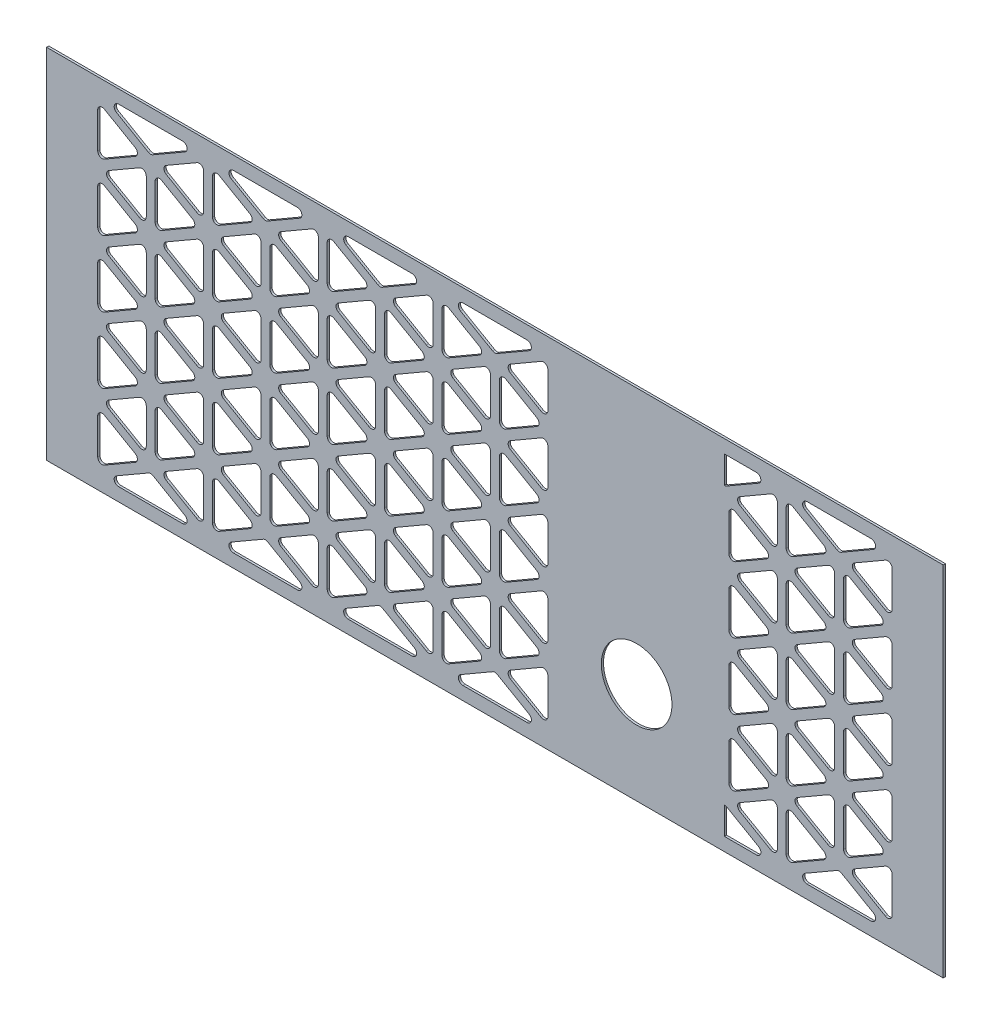
SolidWorks part; units mm, degrees
note: The reader was unsure of these and kept them because the rebuilt part matched: shared geometry of "Sketch3<5>".
ref_plane "Front Plane" through (0, 0, 0) normal (0, 0, 1) x (1, 0, 0)
ref_plane "Top Plane" through (0, 0, 0) normal (0, 1, 0) x (1, 0, 0)
ref_plane "Right Plane" through (0, 0, 0) normal (1, 0, 0) x (0, 0, -1)
sketch "Sketch1" plane through (0, 0, 0) normal (0, 0, 1) x (1, 0, 0)
  line L1 (-101.5, 40.5) -> (101.5, 40.5)
  line L2 (-101.5, 40.5) -> (-101.5, -40.5)
  line L3 (-101.5, -40.5) -> (101.5, -40.5)
  line L4 (101.5, 40.5) -> (101.5, -40.5)
  line L5 (-101.5, 40.5) -> (101.5, -40.5) construction
  line L6 (-101.5, -40.5) -> (101.5, 40.5) construction
  point P0 (0, 0)
  dimension "D1" = 81
  dimension "D2" = 203
extrude "Boss-Extrude1" add sketch "Sketch1" along normal mid plane 0.5
sketch "Sketch3" plane through (0, 0, 0.25) normal (0, 0, 1) x (1, 0, 0)
  line L0 (-90.93, -22.5) -> (-90.93, -37.5) construction
  line L1 (-90.93, -37.5) -> (-77.9396, -30) construction
  line L2 (-77.9396, -30) -> (-90.93, -22.5) construction
  line L3 (-77.9396, -30) -> (-77.9396, -15) construction
  line L4 (-77.9396, -15) -> (-90.93, -22.5) construction
  line L7 (-89.93, -24.2321) -> (-89.93, -35.7679) construction
  line L8 (-89.93, -35.7679) -> (-79.9396, -30) construction
  line L9 (-79.9396, -30) -> (-89.93, -24.2321) construction
  line L10 (-78.9396, -16.7321) -> (-78.9396, -28.2679) construction
  line L11 (-78.9396, -28.2679) -> (-88.93, -22.5) construction
  line L12 (-88.93, -22.5) -> (-78.9396, -16.7321) construction
  line L13 (-101.5, -40.5) -> (101.5, -40.5) construction
  line L15 (-101.5, 40.5) -> (-101.5, -40.5) construction
  line L16 (-90.93, -30) -> (-89.93, -30) construction
  line L17 (-84.4348, -26.25) -> (-84.9348, -27.116) construction
  line L18 (-84.4348, -33.75) -> (-84.9348, -32.884) construction
  line L19 (-89.93, -25.9641) -> (-89.93, -34.0359)
  line L20 (-88.43, -34.9019) -> (-81.4396, -30.866)
  line L21 (-81.4396, -29.134) -> (-88.43, -25.0981)
  line L23 (-78.9396, -18.4641) -> (-78.9396, -26.5359)
  line L24 (-87.43, -23.366) -> (-80.4396, -27.4019)
  line L25 (-87.43, -21.634) -> (-80.4396, -17.5981)
  arc A0 (-88.43, -34.9019) -> (-89.93, -34.0359) centre (-88.93, -34.0359) cw
  arc A1 (-81.4396, -29.134) -> (-81.4396, -30.866) centre (-81.9396, -30) cw
  arc A2 (-89.93, -25.9641) -> (-88.43, -25.0981) centre (-88.93, -25.9641) cw
  arc A4 (-87.43, -23.366) -> (-87.43, -21.634) centre (-86.93, -22.5) cw
  arc A5 (-78.9396, -26.5359) -> (-80.4396, -27.4019) centre (-79.9396, -26.5359) cw
  arc A6 (-78.9396, -18.4641) -> (-80.4396, -17.5981) centre (-79.9396, -18.4641) ccw
  dimension "D7" = 1
  dimension "D9" = 1
  dimension "D1" = 2
  dimension "D2" = 15
  dimension "D3" = 3
  dimension "D4" = 10.57
  dimension "D5" = 1
  dimension "D6" = 1
  dimension "length" = 12.9904
extrude "Cut-Extrude3" cut sketch "Sketch3" against normal through all contours L21 A2 L19 A0 L20 A1
extrude "Cut-Extrude4" cut sketch "Sketch3<5>" against normal through all contours A6 L23 A5 L24 A4 L25
sketch "Sketch3<5>" plane through (0, 0, 0.25) normal (0, 0, 1) x (1, 0, 0) same geometry as "Sketch3"
pattern_linear "LPattern2" count 5 spacing 15 along (0, 1, 0) of "Cut-Extrude3"
pattern_linear "LPattern3" count 4 spacing 15 along (0, 1, 0) of "Cut-Extrude4"
ref_plane "Plane1" through (-77.9396, 0, 0) normal (-1, 0, 0) x (0, 0, 1)
mirror "Mirror1" about plane through (-77.9396, 0, 0) normal (-1, 0, 0) of "LPattern2", "LPattern3", "Cut-Extrude3", "Cut-Extrude4"
pattern_linear "LPattern4" count 7 spacing 25.98 along (1, 0, 0) of "LPattern3", "LPattern2", "Mirror1", "Cut-Extrude3", "Cut-Extrude4"
sketch "Sketch7" plane through (0, 0, 0.25) normal (0, 0, 1) x (1, 0, 0)
  line L0 (-90.93, -37.5) -> (-77.94, -30) construction
  line L1 (-77.94, -30) -> (-64.95, -37.5) construction
  line L2 (-64.95, -37.5) -> (-90.93, -37.5) construction
  line L3 (-101.5, -40.5) -> (101.5, -40.5) construction
  line L4 (-101.5, 40.5) -> (-101.5, -40.5) construction
  line L5 (-78.44, -31.4434) -> (-85.6981, -35.634)
  line L6 (-85.1981, -37.5) -> (-70.6819, -37.5)
  line L7 (-70.1819, -35.634) -> (-77.44, -31.4434)
  arc A0 (-85.1981, -37.5) -> (-85.6981, -35.634) centre (-85.1981, -36.5) cw
  arc A1 (-70.1819, -35.634) -> (-70.6819, -37.5) centre (-70.6819, -36.5) cw
  arc A2 (-77.44, -31.4434) -> (-78.44, -31.4434) centre (-77.94, -32.3094) ccw
  point P9 (-71.445, -33.75)
  dimension "D7" = 1
  dimension "D1" = 10.57
  dimension "D2" = 3
  dimension "D3" = 25.98
  dimension "D4" = 7.5
  dimension "D5" = 1
  dimension "D6" = 1
extrude "Cut-Extrude5" cut sketch "Sketch7" against normal through all
pattern_linear "LPattern5" count 7 spacing 25.98 along (1, 0, 0) of "Cut-Extrude5"
ref_plane "Plane2" [suppressed] through (0, 0, 0) normal (0, -1, 0) x (-1, 0, 0)
mirror "Mirror2" about plane through (0, 0, 0) normal (0, -1, 0) of "LPattern5", "Cut-Extrude5"
sketch "Sketch8" plane through (0, 0, 0.25) normal (0, 0, 1) x (1, 0, 0)
  line L1 (13.99, 40.5) -> (51.96, 40.5)
  line L2 (13.99, 40.5) -> (13.99, -40.5)
  line L3 (13.99, -40.5) -> (51.96, -40.5)
  line L4 (101.5, -40.5) -> (101.5, 40.5)
  line L5 (101.5, 40.5) -> (-101.5, 40.5)
  line L6 (-101.5, 40.5) -> (-101.5, -40.5)
  line L7 (-101.5, -40.5) -> (101.5, -40.5)
  line L8 (101.5, -40.5) -> (101.5, 40.5)
  line L9 (101.5, 40.5) -> (-101.5, 40.5)
  line L10 (-101.5, 40.5) -> (-101.5, -40.5)
  line L11 (-101.5, -40.5) -> (101.5, -40.5)
  line L12 (51.96, 40.5) -> (51.96, -40.5)
  dimension "D2" = 49.54
  dimension "D3" = 37.97
  dimension "D1" = 0
extrude "Boss-Extrude2" add sketch "Sketch8" against normal up to surface (0.5 mm away) contours L12 L1 L2 L3 up to face at (-51.96, 34.9007, -0.25)
sketch "Sketch9" plane through (0, 0, 0.25) normal (0, 0, 1) x (1, 0, 0)
  line L4 (101.5, 40.5) -> (-101.5, 40.5)
  line L5 (-101.5, 40.5) -> (-101.5, -40.5)
  line L6 (-101.5, -40.5) -> (101.5, -40.5)
  line L7 (101.5, -40.5) -> (101.5, 40.5)
  line L8 (101.5, 40.5) -> (-101.5, 40.5)
  line L9 (-101.5, 40.5) -> (-101.5, -40.5)
  line L10 (-101.5, -40.5) -> (101.5, -40.5)
  line L11 (101.5, -40.5) -> (101.5, 40.5)
  circle A0 centre (32.09, -17.62) radius 8
  dimension "D2" = 16
  dimension "D3" = 69.41
  dimension "D4" = 22.88
  dimension "D1" = 0
extrude "Cut-Extrude6" cut sketch "Sketch9" against normal blind 10 contours A0
equation "\"D3@LPattern4\"=2*12.99"
